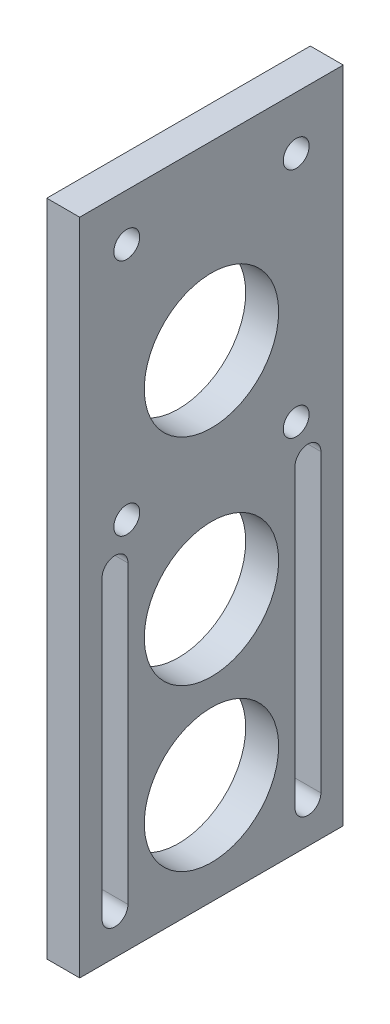
SolidWorks part; units mm, degrees
ref_plane "Front Plane" through (0, 0, 0) normal (0, 0, 1) x (1, 0, 0)
ref_plane "Top Plane" through (0, 0, 0) normal (0, 1, 0) x (1, 0, 0)
ref_plane "Right Plane" through (0, 0, 0) normal (1, 0, 0) x (0, 0, -1)
sketch "Sketch1" plane through (0, 0, 0) normal (1, 0, 0) x (0, 0, -1)
  line L1 (0, 0) -> (56, 0)
  line L2 (0, 0) -> (0, 140)
  line L3 (0, 140) -> (56, 140)
  line L4 (56, 0) -> (56, 140)
  dimension "D1" = 56
  dimension "D2" = 140
extrude "Boss-Extrude1" add sketch "Sketch1" along normal blind 7
sketch "Sketch2" plane through (7, 0, 0) normal (1, 0, 0) x (0, 0, -1)
  line L0 (0, 0) -> (56, 0) construction
  line L1 (28, 0) -> (28, 140) construction
  line L2 (56, 140) -> (0, 140) construction
  circle A0 centre (28, 21.5163) radius 14.275
  circle A1 centre (28, 55.7276) radius 14.275
  circle A2 centre (28, 101.4785) radius 14.275
  point P5 (28, 0)
  dimension "D1" = 28.55
extrude "Cut-Extrude1" cut sketch "Sketch2" against normal through all
sketch "Sketch3" plane through (7, 0, 0) normal (1, 0, 0) x (0, 0, -1)
  line L0 (7.5, 71.2448) -> (7.5, 8.435) construction
  line L1 (10.25, 71.2448) -> (10.25, 8.435)
  line L2 (4.75, 71.2448) -> (4.75, 8.435)
  line L3 (48.5, 8.435) -> (48.5, 71.2448) construction
  line L4 (45.75, 8.435) -> (45.75, 71.2448)
  line L5 (51.25, 8.435) -> (51.25, 71.2448)
  line L6 (0, 140) -> (0, 0) construction
  line L7 (56, 0) -> (56, 140) construction
  arc A0 (10.25, 71.2448) -> (4.75, 71.2448) centre (7.5, 71.2448) ccw
  arc A1 (4.75, 8.435) -> (10.25, 8.435) centre (7.5, 8.435) ccw
  arc A2 (45.75, 8.435) -> (51.25, 8.435) centre (48.5, 8.435) ccw
  arc A3 (51.25, 71.2448) -> (45.75, 71.2448) centre (48.5, 71.2448) ccw
  point P2 (7.5, 39.8399)
  point P7 (48.5, 39.8399)
  dimension "D1" = 2.75
  dimension "D2" = 2.75
  dimension "D3" = 7.5
  dimension "D4" = 7.5
extrude "Cut-Extrude2" cut sketch "Sketch3" against normal through all
sketch "Sketch4" plane through (7, 0, 0) normal (1, 0, 0) x (0, 0, -1)
  line L0 (56, 0) -> (56, 140) construction
  line L1 (0, 140) -> (0, 0) construction
  line L2 (56, 140) -> (0, 140) construction
  circle A0 centre (10, 130) radius 2.75
  circle A1 centre (46, 128.7418) radius 2.75
  circle A2 centre (46, 79.3508) radius 2.75
  circle A3 centre (10, 79.3508) radius 2.75
  point P14 (0, 0)
  point P15 (10, 79.3508)
  dimension "D1" = 5.5
  dimension "D2" = 5.5
  dimension "D9" = 5.5
  dimension "D10" = 5.5
  dimension "D3" = 10
  dimension "D4" = 10
  dimension "D5" = 10
  dimension "D6" = 11.2582
  dimension "D7" = 10
  dimension "D8" = 10
extrude "Cut-Extrude3" cut sketch "Sketch4" against normal through all
